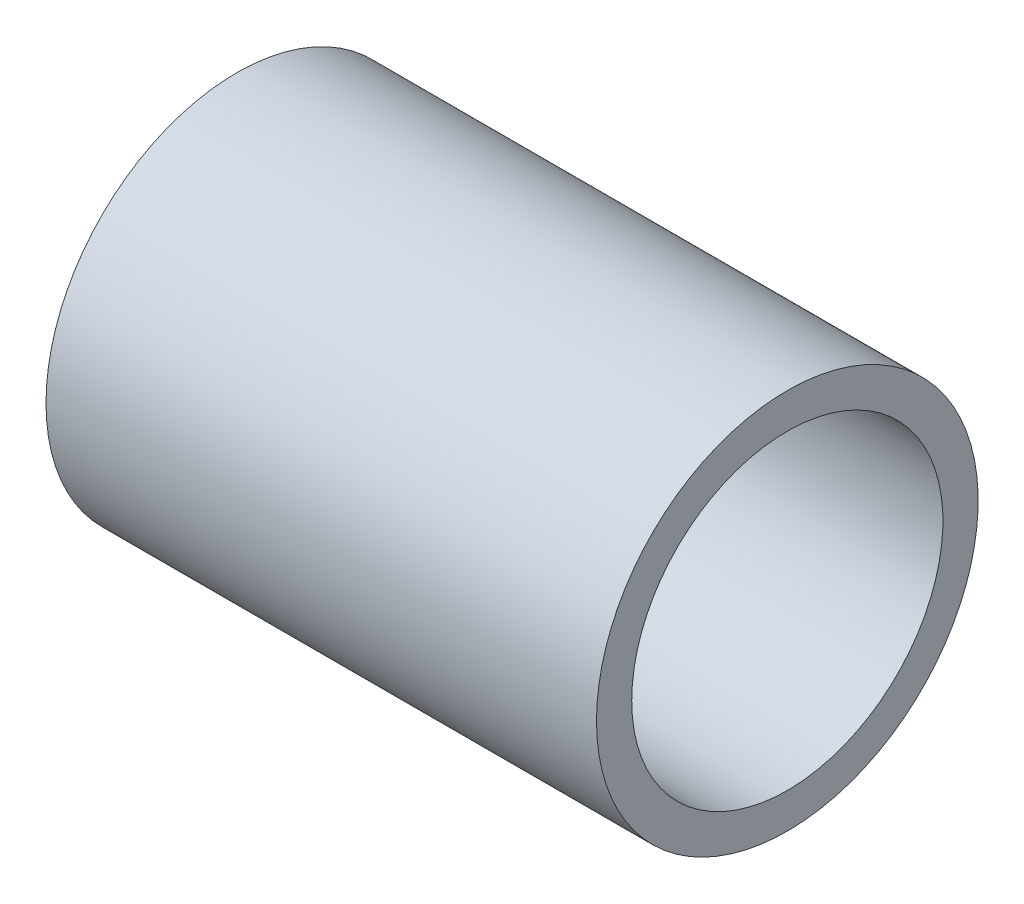
SolidWorks part; units mm, degrees
ref_plane "Front Plane" through (0, 0, 0) normal (0, 0, 1) x (1, 0, 0)
ref_plane "Top Plane" through (0, 0, 0) normal (0, 1, 0) x (1, 0, 0)
ref_plane "Right Plane" through (0, 0, 0) normal (1, 0, 0) x (0, 0, -1)
sketch "Sketch0" plane through (0, 0, 0) normal (0, 0, 1) x (1, 0, 0)
  line L0 (-29.7656, 0) -> (0, 0) construction
  line L2 (-1.1906, 0) -> (0, 0) construction
  line L3 (0, 0) -> (0, 14.4499) construction
  line L4 (-29.7656, 20.6375) -> (-29.7656, -20.6375) construction
  line L5 (-1.1906, 16.637) -> (-29.7656, 16.8275) construction
  line L6 (-1.1906, 16.637) -> (-1.1906, -16.637) construction
  line L7 (-1.1906, -16.637) -> (-29.7656, -16.8275) construction
  line L8 (-29.7656, 16.8275) -> (-29.7656, -16.8275) construction
  line L14 (-1.1906, 13.3223) -> (-1.1906, -13.3223) construction
  dimension "M" = 41.275
  dimension "OD A" = 33.655
  dimension "OD B" = 33.274
  dimension "ID" = 26.6446
  dimension "L" = 59.5312
  dimension "N" = 2.3813
sketch "Sketch1" plane through (0, 0, 0) normal (0, 0, 1) x (1, 0, 0)
  line L0 (-29.7656, 0) -> (0, 0) construction
  line L1 (-29.7656, 0) -> (0, 0) construction
  line L3 (-29.7656, -20.6375) -> (29.7656, -20.6375)
  line L4 (-29.7656, -20.6375) -> (-29.7656, -16.8275)
  line L5 (-29.7656, -16.8275) -> (-1.1906, -16.637)
  line L6 (-1.1906, -13.3223) -> (-1.1906, -16.637)
  line L7 (-1.1906, -13.3223) -> (1.1906, -13.3223)
  line L8 (0, -13.3223) -> (0, -20.6375) construction
  line L9 (1.1906, -13.3223) -> (1.1906, -16.637)
  line L10 (29.7656, -16.8275) -> (1.1906, -16.637)
  line L11 (29.7656, -20.6375) -> (29.7656, -16.8275)
revolve "Revolve1" add sketch "Sketch1" angle 360 about L1
